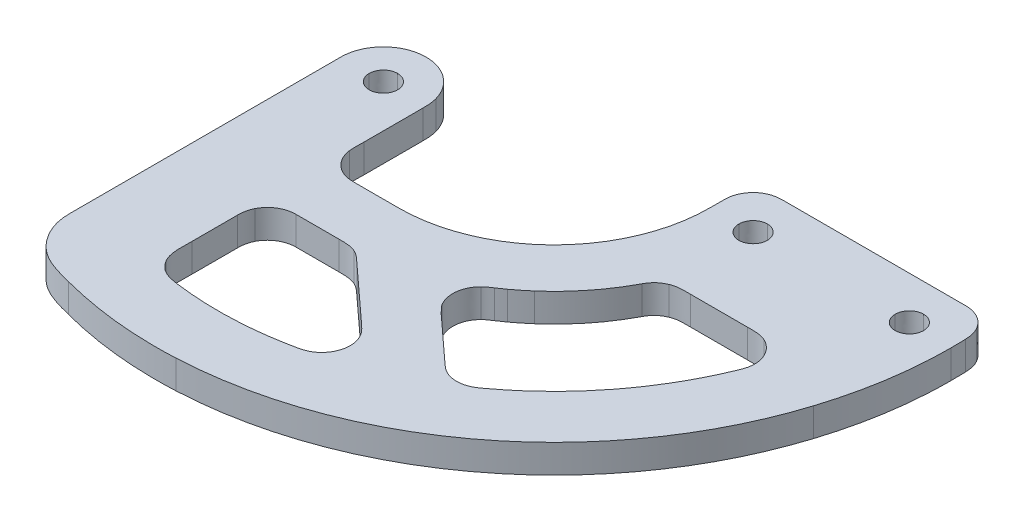
SolidWorks part; units mm, degrees
ref_plane "Front Plane" through (0, 0, 0) normal (0, 0, 1) x (1, 0, 0)
ref_plane "Top Plane" through (0, 0, 0) normal (0, 1, 0) x (1, 0, 0)
ref_plane "Right Plane" through (0, 0, 0) normal (1, 0, 0) x (0, 0, -1)
sketch "Imported Profile" plane through (0, 0, 0) normal (0, 1, 0) x (1, 0, 0)
  spline S0 degree 3 poles (0.2386, 77.0121) (0.1972, 76.9636) (0.2385, 77.0756) (0.2385, 77.1101) knots 0 0 0 0 1 1 1 1
  spline S1 degree 3 poles (0.2385, 77.1101) (0.2385, 77.1451) (0.2385, 77.1721) (0.2385, 77.2066) knots 0 0 0 0 1 1 1 1
  spline S2 degree 3 poles (0.2385, 77.2066) (0.2385, 77.2686) (0.2385, 77.3376) (0.2455, 77.3996) knots 0 0 0 0 1 1 1 1
  spline S3 degree 3 poles (0.2455, 77.3996) (0.2455, 77.5306) (0.2596, 77.6616) (0.2661, 77.7926) knots 0 0 0 0 1 1 1 1
  spline S4 degree 3 poles (0.2661, 77.7926) (0.2936, 78.0611) (0.3212, 78.3231) (0.3695, 78.585) knots 0 0 0 0 1 1 1 1
  spline S5 degree 3 poles (0.3695, 78.585) (0.4591, 79.1362) (0.5969, 79.6736) (0.7829, 80.1973) knots 0 0 0 0 1 1 1 1
  spline S6 degree 3 poles (0.7829, 80.1973) (1.1895, 81.3342) (1.7475, 82.3057) (2.533, 83.2152) knots 0 0 0 0 1 1 1 1
  spline S7 degree 3 poles (2.533, 83.2152) (4.0558, 84.9928) (6.1779, 86.1435) (8.493, 86.4535) knots 0 0 0 0 1 1 1 1
  spline S8 degree 3 poles (8.493, 86.4535) (13.2059, 87.0875) (17.6501, 84.166) (18.9317, 79.584) knots 0 0 0 0 1 1 1 1
  spline S9 degree 3 poles (18.9317, 79.584) (19.228, 78.5298) (19.29, 77.4756) (19.29, 76.387) knots 0 0 0 0 1 1 1 1
  spline S10 degree 3 poles (19.29, 76.387) (19.29, 75.2846) (19.29, 74.1821) (19.29, 73.0797) knots 0 0 0 0 1 1 1 1
  spline S11 degree 3 poles (19.29, 73.0797) (19.29, 70.8748) (19.29, 68.6631) (19.29, 66.4582) knots 0 0 0 0 1 1 1 1
  spline S12 degree 3 poles (19.29, 66.4582) (19.29, 65.3558) (19.29, 64.2534) (19.29, 63.151) knots 0 0 0 0 1 1 1 1
  spline S13 degree 3 poles (19.29, 63.151) (19.29, 62.0623) (19.2004, 60.9736) (19.3313, 59.885) knots 0 0 0 0 1 1 1 1
  spline S14 degree 3 poles (19.3313, 59.885) (19.6, 57.5217) (21.171, 55.5097) (23.3965, 54.6691) knots 0 0 0 0 1 1 1 1
  spline S15 degree 3 poles (23.3965, 54.6691) (24.4576, 54.2696) (25.498, 54.2626) (26.5935, 54.2626) knots 0 0 0 0 1 1 1 1
  spline S16 degree 3 poles (26.5935, 54.2626) (27.6891, 54.2626) (28.7847, 54.2626) (29.8802, 54.2626) knots 0 0 0 0 1 1 1 1
  spline S17 degree 3 poles (29.8802, 54.2626) (32.0506, 54.2626) (34.221, 54.2276) (36.3914, 54.2676) knots 0 0 0 0 1 1 1 1
  spline S18 degree 3 poles (36.3914, 54.2676) (40.8494, 54.3501) (44.9352, 55.1978) (49.0556, 56.8927) knots 0 0 0 0 1 1 1 1
  spline S19 degree 3 poles (49.0556, 56.8927) (57.8199, 60.5033) (64.7377, 67.5174) (68.231, 76.3369) knots 0 0 0 0 1 1 1 1
  spline S20 degree 3 poles (68.231, 76.3369) (69.9053, 80.5743) (70.677, 84.7567) (70.677, 89.318) knots 0 0 0 0 1 1 1 1
  spline S21 degree 3 poles (70.677, 89.318) (70.677, 90.4342) (70.6355, 91.5504) (70.691, 92.6666) knots 0 0 0 0 1 1 1 1
  spline S22 degree 3 poles (70.691, 92.6666) (70.7461, 93.8793) (71.0768, 94.8784) (71.7521, 95.8843) knots 0 0 0 0 1 1 1 1
  spline S23 degree 3 poles (71.7521, 95.8843) (72.4618, 96.9524) (73.3093, 97.662) (74.4875, 98.1788) knots 0 0 0 0 1 1 1 1
  spline S24 degree 3 poles (74.4875, 98.1788) (75.5624, 98.6473) (76.6234, 98.7093) (77.7603, 98.7093) knots 0 0 0 0 1 1 1 1
  spline S25 degree 3 poles (77.7603, 98.7093) (86.752, 98.7093) (95.7506, 98.7093) (104.7423, 98.7093) knots 0 0 0 0 1 1 1 1
  spline S26 degree 3 poles (104.7423, 98.7093) (109.2141, 98.7093) (113.6858, 98.7093) (118.1575, 98.7093) knots 0 0 0 0 1 1 1 1
  spline S27 degree 3 poles (118.1575, 98.7093) (120.5691, 98.7093) (122.7119, 97.5449) (123.8764, 95.402) knots 0 0 0 0 1 1 1 1
  spline S28 degree 3 poles (123.8764, 95.402) (124.4414, 94.3685) (124.6205, 93.3419) (124.6619, 92.1981) knots 0 0 0 0 1 1 1 1
  spline S29 degree 3 poles (124.6619, 92.1981) (124.6964, 91.1025) (124.7169, 90.0139) (124.7099, 88.9183) knots 0 0 0 0 1 1 1 1
  spline S30 degree 3 poles (124.7099, 88.9183) (124.6894, 79.7475) (123.3318, 71.0865) (120.5689, 62.3429) knots 0 0 0 0 1 1 1 1
  spline S31 degree 3 poles (120.5689, 62.3429) (109.3447, 26.8722) (77.2296, 2.1364) (40.0776, 0.3311) knots 0 0 0 0 1 1 1 1
  spline S32 degree 3 poles (40.0776, 0.3311) (30.9137, -0.1169) (22.1907, 0.7927) (13.3162, 3.101) knots 0 0 0 0 1 1 1 1
  spline S33 degree 3 poles (13.3162, 3.101) (8.7686, 4.2861) (4.855, 5.2783) (2.092, 9.8121) knots 0 0 0 0 1 1 1 1
  spline S34 degree 3 poles (2.092, 9.8121) (0.8449, 11.8515) (0.2661, 13.8635) (0.2386, 16.2613) knots 0 0 0 0 1 1 1 1
  spline S35 degree 3 poles (0.2386, 16.2613) (0.2111, 18.4869) (0.2386, 20.7192) (0.2386, 22.9516) knots 0 0 0 0 1 1 1 1
  spline S36 degree 3 poles (0.2386, 22.9516) (0.2386, 40.9695) (0.2386, 58.9942) (0.2386, 77.0121) knots 0 0 0 0 1 1 1 1
  spline S37 degree 3 poles (77.7944, 66.8094) (75.0315, 61.614) (71.6002, 57.287) (67.1766, 53.4009) knots 0 0 0 0 1 1 1 1
  spline S38 degree 3 poles (67.1766, 53.4009) (66.1087, 52.457) (64.9925, 51.5681) (63.8349, 50.7207) knots 0 0 0 0 1 1 1 1
  spline S39 degree 3 poles (63.8349, 50.7207) (63.263, 50.3002) (62.6773, 49.8939) (62.0848, 49.5011) knots 0 0 0 0 1 1 1 1
  spline S40 degree 3 poles (62.0848, 49.5011) (61.4922, 49.1081) (60.8928, 48.7432) (60.3898, 48.2333) knots 0 0 0 0 1 1 1 1
  spline S41 degree 3 poles (60.3898, 48.2333) (58.2539, 46.1042) (57.9093, 42.7762) (59.563, 40.2613) knots 0 0 0 0 1 1 1 1
  spline S42 degree 3 poles (59.563, 40.2613) (60.1486, 39.3656) (61.8298, 37.9118) (62.5878, 37.2227) knots 0 0 0 0 1 1 1 1
  spline S43 degree 3 poles (62.5878, 37.2227) (63.6489, 36.2512) (64.71, 35.2797) (65.7642, 34.3082) knots 0 0 0 0 1 1 1 1
  spline S44 degree 3 poles (65.7642, 34.3082) (66.8252, 33.3436) (67.8863, 32.3721) (68.9405, 31.4005) knots 0 0 0 0 1 1 1 1
  spline S45 degree 3 poles (68.9405, 31.4005) (69.4711, 30.918) (70.0016, 30.429) (70.5322, 29.9468) knots 0 0 0 0 1 1 1 1
  spline S46 degree 3 poles (70.5322, 29.9468) (71.0489, 29.4643) (71.5519, 28.9614) (72.11, 28.5273) knots 0 0 0 0 1 1 1 1
  spline S47 degree 3 poles (72.11, 28.5273) (73.3847, 27.5421) (74.618, 27.1493) (76.2235, 27.2044) knots 0 0 0 0 1 1 1 1
  spline S48 degree 3 poles (76.2235, 27.2044) (77.7806, 27.2664) (78.952, 27.8452) (80.1647, 28.7409) knots 0 0 0 0 1 1 1 1
  spline S49 degree 3 poles (80.1647, 28.7409) (82.4522, 30.4221) (84.6295, 32.2136) (86.7172, 34.1497) knots 0 0 0 0 1 1 1 1
  spline S50 degree 3 poles (86.7172, 34.1497) (90.9685, 38.084) (94.6478, 42.3697) (97.8931, 47.1722) knots 0 0 0 0 1 1 1 1
  spline S51 degree 3 poles (97.8931, 47.1722) (99.5123, 49.57) (100.9799, 52.0366) (102.3166, 54.5998) knots 0 0 0 0 1 1 1 1
  spline S52 degree 3 poles (102.3166, 54.5998) (103.0539, 56.0261) (105.3827, 60.801) (105.7479, 62.4202) knots 0 0 0 0 1 1 1 1
  spline S53 degree 3 poles (105.7479, 62.4202) (106.4163, 65.3485) (104.9418, 68.3389) (102.2201, 69.5929) knots 0 0 0 0 1 1 1 1
  spline S54 degree 3 poles (102.2201, 69.5929) (100.8283, 70.2336) (99.4572, 70.1785) (98.0172, 70.1785) knots 0 0 0 0 1 1 1 1
  spline S55 degree 3 poles (98.0172, 70.1785) (96.5977, 70.1785) (95.1715, 70.1785) (93.7521, 70.1785) knots 0 0 0 0 1 1 1 1
  spline S56 degree 3 poles (93.7521, 70.1785) (90.8927, 70.1785) (88.0401, 70.1785) (85.1876, 70.1785) knots 0 0 0 0 1 1 1 1
  spline S57 degree 3 poles (85.1876, 70.1785) (83.7476, 70.1785) (82.3626, 70.275) (80.957, 69.6895) knots 0 0 0 0 1 1 1 1
  spline S58 degree 3 poles (80.957, 69.6895) (79.4963, 69.0763) (78.5386, 68.2081) (77.7944, 66.8094) knots 0 0 0 0 1 1 1 1
  spline S59 degree 3 poles (25.6357, 41.5636) (27.7923, 41.5636) (29.949, 41.5636) (32.0987, 41.5636) knots 0 0 0 0 1 1 1 1
  spline S60 degree 3 poles (32.0987, 41.5636) (33.1735, 41.5636) (34.2553, 41.5636) (35.3302, 41.5636) knots 0 0 0 0 1 1 1 1
  spline S61 degree 3 poles (35.3302, 41.5636) (36.6669, 41.5636) (37.9347, 41.5786) (39.2231, 40.9917) knots 0 0 0 0 1 1 1 1
  spline S62 degree 3 poles (39.2231, 40.9917) (40.298, 40.4957) (41.0835, 39.7032) (41.9241, 38.9246) knots 0 0 0 0 1 1 1 1
  spline S63 degree 3 poles (41.9241, 38.9246) (42.7647, 38.1598) (43.6053, 37.3881) (44.4459, 36.6164) knots 0 0 0 0 1 1 1 1
  spline S64 degree 3 poles (44.4459, 36.6164) (46.1271, 35.0799) (47.8083, 33.5434) (49.4895, 32) knots 0 0 0 0 1 1 1 1
  spline S65 degree 3 poles (49.4895, 32) (51.1501, 30.4773) (52.8175, 28.9476) (54.4849, 27.4249) knots 0 0 0 0 1 1 1 1
  spline S66 degree 3 poles (54.4849, 27.4249) (55.3324, 26.6463) (56.1041, 25.8746) (56.5864, 24.786) knots 0 0 0 0 1 1 1 1
  spline S67 degree 3 poles (56.5864, 24.786) (57.0894, 23.6629) (57.241, 22.6018) (57.0894, 21.3822) knots 0 0 0 0 1 1 1 1
  spline S68 degree 3 poles (57.0894, 21.3822) (56.7862, 19.0464) (55.2153, 17.069) (53.0104, 16.249) knots 0 0 0 0 1 1 1 1
  spline S69 degree 3 poles (53.0104, 16.249) (51.7909, 15.7875) (47.6223, 15.1121) (46.3614, 14.933) knots 0 0 0 0 1 1 1 1
  spline S70 degree 3 poles (46.3614, 14.933) (41.8207, 14.2853) (37.3146, 14.0579) (32.7395, 14.2371) knots 0 0 0 0 1 1 1 1
  spline S71 degree 3 poles (32.7395, 14.2371) (30.4795, 14.3266) (28.2402, 14.5196) (26.0009, 14.8158) knots 0 0 0 0 1 1 1 1
  spline S72 degree 3 poles (26.0009, 14.8158) (23.5204, 15.1398) (21.6187, 15.6358) (20.1924, 18.006) knots 0 0 0 0 1 1 1 1
  spline S73 degree 3 poles (20.1924, 18.006) (18.9729, 20.0386) (19.2898, 22.6086) (19.2898, 24.6895) knots 0 0 0 0 1 1 1 1
  spline S74 degree 3 poles (19.2898, 24.6895) (19.2898, 26.9632) (19.2898, 29.2371) (19.2898, 31.5108) knots 0 0 0 0 1 1 1 1
  spline S75 degree 3 poles (19.2898, 31.5108) (19.2898, 32.627) (19.2898, 33.7432) (19.2898, 34.8664) knots 0 0 0 0 1 1 1 1
  spline S76 degree 3 poles (19.2898, 34.8664) (19.2898, 36.017) (19.4482, 37.0505) (19.9788, 38.1047) knots 0 0 0 0 1 1 1 1
  spline S77 degree 3 poles (19.9788, 38.1047) (21.0675, 40.2269) (23.2517, 41.5636) (25.6357, 41.5636) knots 0 0 0 0 1 1 1 1
  spline S78 degree 3 poles (83.3824, 89.1886) (83.3824, 90.9387) (81.9561, 92.365) (80.206, 92.365) knots 0 0 0 0 1 1 1 1
  spline S79 degree 3 poles (80.206, 92.365) (78.4559, 92.365) (77.0296, 90.9387) (77.0296, 89.1886) knots 0 0 0 0 1 1 1 1
  spline S80 degree 3 poles (77.0296, 89.1886) (77.0296, 87.4316) (78.4559, 86.0122) (80.206, 86.0122) knots 0 0 0 0 1 1 1 1
  spline S81 degree 3 poles (80.206, 86.0122) (81.9561, 86.0122) (83.3824, 87.4316) (83.3824, 89.1886) knots 0 0 0 0 1 1 1 1
  spline S82 degree 3 poles (12.9371, 77.0136) (12.9371, 78.7706) (11.5177, 80.19) (9.7607, 80.19) knots 0 0 0 0 1 1 1 1
  spline S83 degree 3 poles (9.7607, 80.19) (8.0106, 80.19) (6.5843, 78.7706) (6.5843, 77.0136) knots 0 0 0 0 1 1 1 1
  spline S84 degree 3 poles (6.5843, 77.0136) (6.5843, 75.2635) (8.0106, 73.8372) (9.7607, 73.8372) knots 0 0 0 0 1 1 1 1
  spline S85 degree 3 poles (9.7607, 73.8372) (11.5177, 73.8372) (12.9371, 75.2635) (12.9371, 77.0136) knots 0 0 0 0 1 1 1 1
  spline S86 degree 3 poles (118.3019, 89.1886) (118.3019, 90.9387) (116.8825, 92.365) (115.1324, 92.365) knots 0 0 0 0 1 1 1 1
  spline S87 degree 3 poles (115.1324, 92.365) (113.3754, 92.365) (111.956, 90.9387) (111.956, 89.1886) knots 0 0 0 0 1 1 1 1
  spline S88 degree 3 poles (111.956, 89.1886) (111.956, 87.4316) (113.3754, 86.0122) (115.1324, 86.0122) knots 0 0 0 0 1 1 1 1
  spline S89 degree 3 poles (115.1324, 86.0122) (116.8825, 86.0122) (118.3019, 87.4316) (118.3019, 89.1886) knots 0 0 0 0 1 1 1 1
extrude "Boss-Extrude1" add sketch "Imported Profile" along normal blind 6.35
sketch "Sketch1" plane through (0, 6.35, 0) normal (0, 1, 0) x (1, 0, 0)
  circle A0 centre (9.7607, 77.0136) radius 3.1764
  circle A1 centre (115.1324, 89.1886) radius 3.1764
  circle A2 centre (80.206, 89.1886) radius 3.1764
